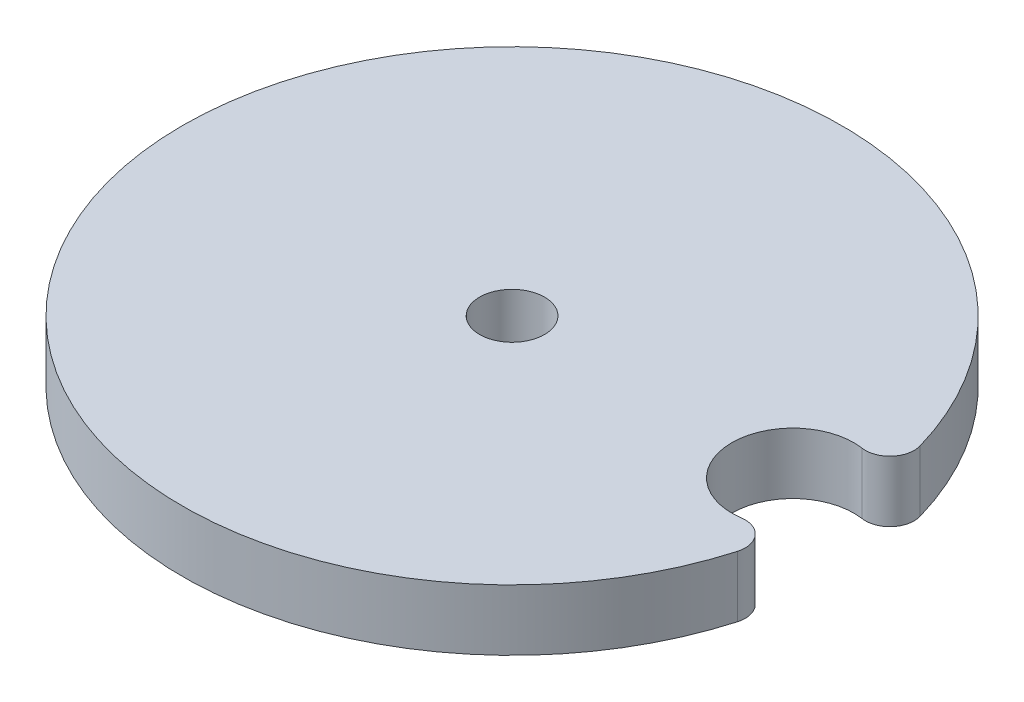
SolidWorks part; units mm, degrees
material "1023 Carbon Steel Sheet (SS)"
ref_plane "Front Plane" through (0, 0, 0) normal (0, 0, 1) x (1, 0, 0)
ref_plane "Top Plane" through (0, 0, 0) normal (0, 1, 0) x (1, 0, 0)
ref_plane "Right Plane" through (0, 0, 0) normal (1, 0, 0) x (0, 0, -1)
sketch "Sketch1" plane through (0, 0, 0) normal (0, 1, 0) x (1, 0, 0)
  circle A0 centre (0, 0) radius 34.29
  circle A1 centre (29.21, 0) radius 6.35
  point P5 (0, 0)
  dimension "D1" = 68.58
  dimension "D2" = 12.7
  dimension "D3" = 29.21
extrude "Boss-Extrude1" add sketch "Sketch1" along normal blind 6.35 contours A1 A0 region at (-0.9652, 0, 0)
hole_wizard "1/4 Clearance Hole1" positions "Sketch2" profile "Sketch3" hole size "1/4" standard "ANSI Inch" end condition through all
sketch "Sketch2" plane through (0, 6.35, 0) normal (0, 1, 0) x (1, 0, 0)
  point P0 (0, 0)
sketch "Sketch3" plane through (0, 6.35, 0) normal (1, 0, 0) x (0, 0, 1)
  line L0 (0, 0) -> (0, 6.35)
  line L1 (0, 6.35) -> (3.3782, 6.35)
  line L2 (3.3782, 6.35) -> (3.3782, 0)
  line L5 (3.3782, 0) -> (0, 0)
  line L11 (0, -6.35) -> (0, 107.95) construction
  dimension "Thru Hole Dia." = 6.7564
  dimension "Thru Hole Depth" = 6.35
fillet "Fillet1" radius 2.54 2 edges at (34.0415, 3.175, 4.1205) (34.0415, 3.175, -4.1205)
